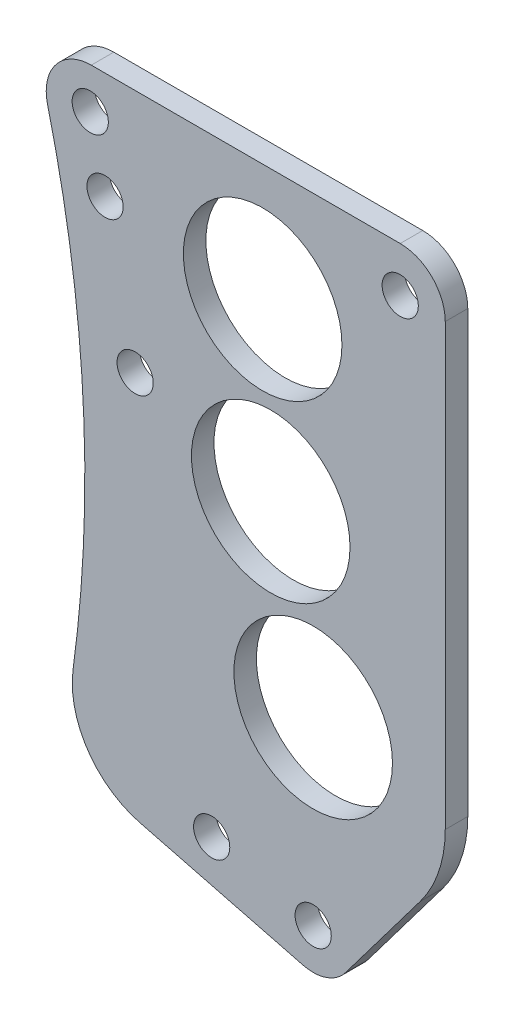
SolidWorks part; units mm, degrees
material "Polypropylene"
ref_plane "Front Plane" through (0, 0, 0) normal (0, 0, 1) x (1, 0, 0)
ref_plane "Top Plane" through (0, 0, 0) normal (0, 1, 0) x (1, 0, 0)
ref_plane "Right Plane" through (0, 0, 0) normal (1, 0, 0) x (0, 0, -1)
sketch "Sketch2" plane through (0, 0, 0) normal (0, 0, 1) x (1, 0, 0)
  line L0 (-139.7, 0) -> (139.7, 0) construction
  line L1 (-139.7, 162.1582) -> (139.7, 162.1582) construction
  line L2 (-139.7, 0) -> (-139.7, 162.1582) construction
  line L3 (89.6578, 156.3951) -> (-88.9, 111.3582) construction
  line L4 (-88.9, 111.3582) -> (87.5277, 58.5898) construction
  line L6 (85.725, 52.9003) -> (82.55, 52.9003) construction
  line L7 (139.7, 162.1582) -> (139.7, 0) construction
  line L8 (-109.7, 30) -> (-102.2692, 59.0652) construction
  line L9 (-102.2692, 59.0652) -> (-101.4828, 62.1412) construction
  line L10 (-101.4828, 62.1412) -> (-88.9, 111.3582) construction
  line L11 (-88.9, 111.3582) -> (85.725, 52.9003) construction
  line L12 (82.55, 52.9003) -> (82.55, 64.2654) construction
  line L13 (-88.9, 111.3582) -> (91.7477, 147.1022) construction
  line L14 (82.55, 52.9003) -> (85.725, 0) construction
  line L15 (85.725, 52.9003) -> (92.4089, 52.9003) construction
  line L16 (-131.5562, 154.0144) -> (-88.9, 111.3582) construction
  line L17 (-88.9, 111.3582) -> (88.9, 111.3582) construction
  line L18 (-88.9, 111.3582) -> (88.1045, 162.1582) construction
  line L22 (82.8416, 162.1582) -> (82.8416, 157.3763) construction
  line L23 (82.8416, 157.3763) -> (-88.9, 111.3582) construction
  line L24 (122.2, 93.8006) -> (115.1001, 121.5451) construction
  line L25 (-88.9, 111.3582) -> (-131.5562, 68.702) construction
  line L26 (120.5994, 121.5451) -> (117.8497, 126.3076) construction
  line L27 (117.8497, 126.3076) -> (112.3505, 126.3076) construction
  line L28 (112.3505, 126.3076) -> (109.6008, 121.5451) construction
  line L29 (109.6008, 121.5451) -> (112.3505, 116.7826) construction
  line L30 (112.3505, 116.7826) -> (117.8497, 116.7826) construction
  line L31 (117.8497, 116.7826) -> (120.5994, 121.5451) construction
  line L40 (-139.7, 154.0144) -> (-139.7, 30) construction
  line L41 (-131.5562, 161.3468) -> (-137.9062, 157.6806) construction
  line L42 (-137.9062, 157.6806) -> (-137.9062, 150.3483) construction
  line L43 (-137.9062, 150.3483) -> (-131.5562, 146.6821) construction
  line L44 (-131.5562, 146.6821) -> (-125.2062, 150.3483) construction
  line L45 (-125.2062, 150.3483) -> (-125.2062, 157.6806) construction
  line L46 (-125.2062, 157.6806) -> (-131.5562, 161.3468) construction
  line L47 (-131.5562, 61.3697) -> (-125.2062, 65.0358) construction
  line L48 (-125.2062, 65.0358) -> (-125.2062, 72.3682) construction
  line L49 (-125.2062, 72.3682) -> (-131.5562, 76.0344) construction
  line L50 (-131.5562, 76.0344) -> (-137.9062, 72.3682) construction
  line L51 (-137.9062, 72.3682) -> (-137.9062, 65.0358) construction
  line L52 (-137.9062, 65.0358) -> (-131.5562, 61.3697) construction
  line L53 (-79.9907, 25.8335) -> (-68.3996, 108.4832) construction
  line L54 (-77.6298, 128.7224) -> (-127.1225, 160.8455) construction
  line L56 (89.8048, 162.1582) -> (133.35, 162.1582)
  line L57 (139.7, 155.8082) -> (139.7, 93.8006)
  line L59 (137.8401, 160.2984) -> (129.3001, 151.7583) construction
  line L60 (122.2, 93.8006) -> (110.579, 80.7162) construction
  line L61 (110.579, 80.7162) -> (106.7754, 76.4337) construction
  line L62 (98.6364, 77.8864) -> (101.1368, 77.4401) construction
  line L63 (98.6364, 77.8864) -> (-88.9, 111.3582) construction
  line L64 (106.7754, 76.4337) -> (108.5394, 70.9844) construction
  line L65 (113.9624, 145.6482) -> (95.9884, 127.7012) construction
  line L66 (115.1001, 121.5451) -> (104.4623, 124.9716) construction
  line L67 (95.9884, 127.7012) -> (98.4182, 126.9185) construction
  line L68 (98.4182, 126.9185) -> (104.4623, 124.9716) construction
  line L69 (101.1368, 77.4401) -> (106.7754, 76.4337) construction
  line L70 (121.0823, 72.7684) -> (121.0823, 98.1684) construction
  line L71 (125.6552, 69.3194) -> (136.1716, 83.2629)
  line L72 (96.6729, 73.1093) -> (119.6608, 67.2199)
  line L73 (106.7754, 76.4337) -> (121.0823, 72.7684) construction
  circle A0 centre (-88.9, 111.3582) radius 50.8 construction
  circle A1 centre (-88.9, 111.3582) radius 14.351 construction
  arc A15 (81.4439, 60.4094) -> (81.4884, 162.1582) centre (-88.9, 111.3582) ccw construction
  arc A16 (92.4089, 52.9003) -> (94.7018, 162.1582) centre (-88.9, 111.3582) ccw construction
  arc A17 (89.6578, 156.3951) -> (87.5277, 58.5898) centre (-88.9, 111.3582) cw construction
  arc A18 (90.2045, 57.7892) -> (92.367, 157.0784) centre (-88.9, 111.3582) ccw construction
  arc A19 (84.8508, 59.3905) -> (86.9487, 155.7118) centre (-88.9, 111.3582) ccw construction
  arc A20 (84.8508, 59.3905) -> (90.2045, 57.7892) centre (87.5277, 58.5898) ccw construction
  arc A21 (92.367, 157.0784) -> (86.9487, 155.7118) centre (89.6578, 156.3951) ccw construction
  arc A23 (89.6578, 156.3951) -> (88.1045, 162.1582) centre (-88.9, 111.3582) ccw construction
  circle A24 centre (113.9624, 145.6482) radius 15.24 construction
  circle A25 centre (122.2, 93.8006) radius 17.5 construction
  circle A26 centre (122.2, 93.8006) radius 4.826 construction
  circle A27 centre (115.1001, 121.5451) radius 23.8125 construction
  circle A28 centre (113.9624, 145.6482) radius 16.51 construction
  circle A29 centre (-109.7, 30) radius 30 construction
  circle A30 centre (-109.7, 30) radius 25.4 construction
  circle A31 centre (-109.7, 55.4) radius 2.5527 construction
  circle A32 centre (-97, 51.997) radius 2.5527 construction
  circle A33 centre (-87.703, 42.7) radius 2.5527 construction
  circle A34 centre (-84.3, 30) radius 2.5527 construction
  circle A35 centre (-87.703, 17.3) radius 2.5527 construction
  circle A36 centre (-97, 8.003) radius 2.5527 construction
  circle A37 centre (-109.7, 4.6) radius 2.5527 construction
  circle A38 centre (-122.4, 8.003) radius 2.5527 construction
  circle A39 centre (-131.697, 17.3) radius 2.5527 construction
  circle A40 centre (-135.1, 30) radius 2.5527 construction
  circle A41 centre (-131.697, 42.7) radius 2.5527 construction
  circle A42 centre (-122.4, 51.997) radius 2.5527 construction
  arc A43 (87.5277, 58.5898) -> (85.725, 52.9003) centre (-88.9, 111.3582) cw construction
  circle A44 centre (-109.7, 30) radius 14.351 construction
  circle A48 centre (115.1001, 121.5451) radius 24.5999 construction
  circle A54 centre (115.1001, 121.5451) radius 4.7625 construction
  circle A55 centre (115.1001, 121.5451) radius 8.89 construction
  circle A56 centre (115.1001, 121.5451) radius 10.16 construction
  circle A59 centre (113.9624, 145.6482) radius 15.24 construction
  circle A60 centre (113.9624, 145.6482) radius 16.51 construction
  circle A61 centre (89.6578, 156.3951) radius 2.5527
  circle A62 centre (91.7477, 147.1022) radius 2.5527
  circle A63 centre (-131.5562, 68.702) radius 3.175 construction
  circle A64 centre (-131.5562, 154.0144) radius 3.175 construction
  circle A65 centre (-131.5562, 154.0144) radius 6.35 construction
  circle A66 centre (-131.5562, 68.702) radius 6.35 construction
  arc A67 (-139.7, 30) -> (-79.9907, 25.8335) centre (-109.7, 30) ccw construction
  arc A69 (-127.1225, 160.8455) -> (-139.7, 154.0144) centre (-131.5562, 154.0144) ccw construction
  arc A70 (-68.3996, 108.4832) -> (-77.6298, 128.7224) centre (-88.9, 111.3582) ccw construction
  arc A71 (139.7, 93.8006) -> (136.1716, 83.2629) centre (122.2, 93.8006) cw
  arc A72 (83.6426, 154.2755) -> (87.2431, 87.1417) centre (-88.9, 111.3582) cw
  arc A73 (87.2431, 87.1417) -> (96.6729, 73.1093) centre (99.8248, 85.4119) ccw
  arc A74 (133.35, 162.1582) -> (139.7, 155.8082) centre (133.35, 155.8082) cw
  circle A76 centre (106.7754, 76.4337) radius 2.5527
  circle A82 centre (115.1001, 121.5451) radius 11.176
  arc A83 (83.6426, 154.2755) -> (89.8048, 162.1582) centre (89.8048, 155.8082) cw
  circle A84 centre (113.9624, 145.6482) radius 11.176
  circle A87 centre (133.35, 155.8082) radius 2.5527
  circle A88 centre (95.9884, 127.7012) radius 2.5527
  circle A89 centre (121.0823, 72.7684) radius 2.5527
  arc A90 (119.6608, 67.2199) -> (125.6552, 69.3194) centre (121.0823, 72.7684) ccw
  circle A91 centre (121.0823, 98.1684) radius 15.24 construction
  circle A92 centre (121.0823, 98.1684) radius 16.51 construction
  circle A93 centre (121.0823, 98.1684) radius 11.176
  point P6 (-88.9, 60.5582)
  point P10 (-109.7, 0)
  point P11 (86.727, 55.913)
  point P30 (-88.9, 111.3582)
  point P32 (0, 0)
  point P36 (0, 162.1582)
  point P37 (-88.9, 162.1582)
  point P42 (95.2063, 107.3484)
  point P66 (-109.7, 30)
  point P68 (-139.7, 30)
  point P82 (88.954, 159.099)
  point P85 (-79.7, 30)
  point P92 (88.1045, 162.1582)
  point P105 (122.2, 93.8006)
  point P138 (132.0087, 101.5491)
  point P142 (107.5616, 74.0051)
  point P171 (130.9475, 102.7298)
  dimension "D1" = 101.6
  dimension "D2" = 28.702
  dimension "D3" = 60
  dimension "D4" = 50.8
  dimension "D9" = 127
  dimension "D10" = 12.7
  dimension "D11" = 6.35
  dimension "D12" = 2.794
  dimension "D16" = 35
  dimension "D17" = 9.652
  dimension "D18" = 47.625
  dimension "D19" = 30.48
  dimension "D20" = 30.48
  dimension "D5" = 5.1054
  dimension "D13" = 85.725
  dimension "D25" = 28.702
  dimension "D21" = 82.55
  dimension "D22" = 186.944
  dimension "D30" = 49.1998
  dimension "D31" = 60.325
  dimension "D32" = 27.844
  dimension "D33" = 12.7
  dimension "D34" = 1.27
  dimension "D35" = 25.4
  dimension "D37" = 9.525
  dimension "D38" = 17.78
  dimension "D39" = 20.32
  dimension "D40" = 6.35
  dimension "D41" = 6.35
  dimension "D42" = 1.27
  dimension "D43" = 1.27
  dimension "D44" = 12.7
  dimension "D45" = 3.175
  dimension "D28" = 5.1054
  dimension "D29" = 6.35
  dimension "D47" = 22.352
  dimension "D48" = 6.35
  dimension "D49" = 22.352
  dimension "D52" = 25.4
  dimension "D53" = 5.1054
  dimension "D51" = 5.1054
  dimension "D55" = 2.54
  dimension "D56" = 1.5875
  dimension "D36" = 3.175
  dimension "D6" = 12
  dimension "D7" = 15
  dimension "D8" = 279.4
  dimension "D14" = 3.175
  dimension "D15" = 279.4
  dimension "D23" = 3.175
  dimension "D24" = 3.175
  dimension "D26" = 3.175
  dimension "D27" = 9.525
  dimension "D50" = 12.0774
  dimension "D54" = 6.35
extrude "Boss-Extrude1" add sketch "Sketch2" along normal blind 3.175
